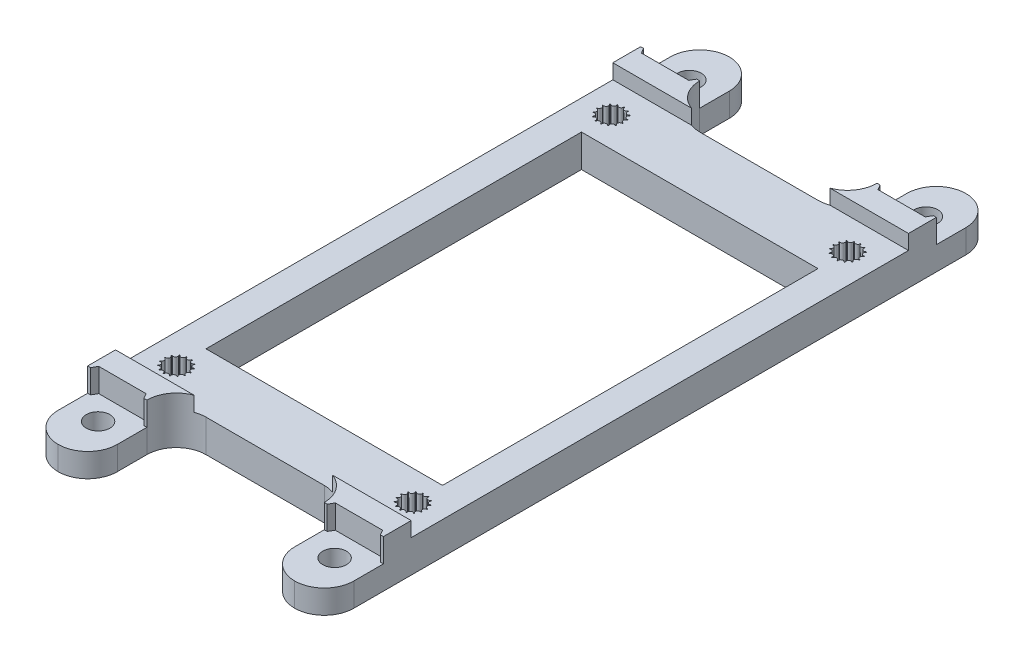
SolidWorks part; units mm, degrees
ref_plane "Front Plane" through (0, 0, 0) normal (0, 0, 1) x (1, 0, 0)
ref_plane "Top Plane" through (0, 0, 0) normal (0, 1, 0) x (1, 0, 0)
ref_plane "Right Plane" through (0, 0, 0) normal (1, 0, 0) x (0, 0, -1)
sketch "Sketch1" plane through (0, 0, 0) normal (0, 1, 0) x (1, 0, 0)
  line L1 (0, 0) -> (50, 0)
  line L2 (0, 0) -> (0, 83.5)
  line L3 (0, 83.5) -> (50, 83.5)
  line L4 (50, 0) -> (50, 83.5)
  dimension "D1" = 50
  dimension "D2" = 83.5
extrude "Boss-Extrude1" add sketch "Sketch1" along normal blind 8
sketch "Sketch2" plane through (0, 8, 0) normal (0, 1, 0) x (1, 0, 0)
  line L4 (0, 83.5) -> (0, 0)
  line L5 (0, 0) -> (50, 0)
  line L6 (50, 0) -> (50, 83.5)
  line L7 (50, 83.5) -> (0, 83.5)
  line L8 (0, 83.5) -> (0, 0)
  line L9 (0, 0) -> (50, 0)
  line L10 (50, 0) -> (50, 83.5)
  line L11 (50, 83.5) -> (0, 83.5)
  circle A0 centre (5, 5) radius 2.25
  circle A1 centre (5, 7.25) radius 0.4
  circle A2 centre (5.9152, 7.0555) radius 0.4
  circle A3 centre (6.6721, 6.5055) radius 0.4
  circle A4 centre (7.1399, 5.6953) radius 0.4
  circle A5 centre (7.2377, 4.7648) radius 0.4
  circle A6 centre (6.9486, 3.875) radius 0.4
  circle A7 centre (6.3225, 3.1797) radius 0.4
  circle A8 centre (5.4678, 2.7992) radius 0.4
  circle A9 centre (4.5322, 2.7992) radius 0.4
  circle A10 centre (3.6775, 3.1797) radius 0.4
  circle A11 centre (3.0514, 3.875) radius 0.4
  circle A12 centre (2.7623, 4.7648) radius 0.4
  circle A13 centre (2.8601, 5.6953) radius 0.4
  circle A14 centre (3.3279, 6.5055) radius 0.4
  circle A15 centre (4.0848, 7.0555) radius 0.4
  point P38 (5, 5)
  dimension "D4" = 4.5
  dimension "D5" = 0.8
  dimension "D2" = 5
  dimension "D3" = 5
  dimension "D1" = 0
  dimension "D6" = 15
extrude "Cut-Extrude1" cut sketch "Sketch2" against normal blind 8 contours A15 A0 A14 A13 A12 A11 A10 A9 A8 A7 A6 A5 A4 A3 A2 A1
ref_plane "Plane1" through (25, 0, 0) normal (-1, 0, 0) x (0, 0, 1)
ref_plane "Plane2" through (0, 0, -41.75) normal (0, 0, -1) x (-1, 0, 0)
mirror "Mirror1" about plane through (0, 0, -41.75) normal (0, 0, -1) of "Cut-Extrude1" second plane through (25, 0, 0) second plane normal (-1, 0, 0)
sketch "Sketch3" plane through (0, 8, 0) normal (0, 1, 0) x (1, 0, 0)
  line L1 (0, 0) -> (10, 0)
  line L2 (0, 0) -> (0, -15)
  line L3 (0, -15) -> (10, -15)
  line L4 (10, 0) -> (10, -15)
  circle A0 centre (5, -8.25) radius 2
  dimension "D3" = 4
  dimension "D1" = 15
  dimension "D2" = 10
  dimension "D4" = 5
  dimension "D5" = 8.25
extrude "Boss-Extrude2" add sketch "Sketch3" against normal blind 8
mirror "Mirror2" about plane through (0, 0, -41.75) normal (0, 0, -1) of "Boss-Extrude2" second plane through (25, 0, 0) second plane normal (-1, 0, 0)
fillet "Fillet1" radius 5 20 edges at (0, 4, 15) (10, 4, 0) (5, 0, 15) (10, 4, 15) (5, 8, 15) (45, 0, 15) (45, 8, 15) (50, 4, 15) (40, 4, 15) (40, 4, 0) (5, 0, -98.5) (5, 8, -98.5) (0, 4, -98.5) (10, 4, -98.5) (10, 4, -83.5) (50, 4, -98.5) (40, 4, -83.5) (45, 0, -98.5) (40, 4, -98.5) (45, 8, -98.5)
sketch "Sketch4" plane through (0, 8, 0) normal (0, 1, 0) x (1, 0, 0)
  line L0 (0.5, -5) -> (0, -5)
  line L1 (0, -5) -> (0.5, -5)
  line L2 (9.5, -5) -> (15, -5)
  line L3 (15, -5) -> (15, -18.6205)
  line L4 (15, -18.6205) -> (0, -18.6205)
  line L5 (0, -18.6205) -> (0, -5)
  line L6 (0.5, -5) -> (1, -4.134)
  line L7 (1, -4.134) -> (9, -4.134)
  line L8 (5, -5) -> (5, -3.4503) construction
  line L9 (9.5, -5) -> (9, -4.134)
  arc A0 (9.5, -5) -> (0.5, -5) centre (5, -5) ccw
  point P11 (5, -4.134)
  dimension "D1" = 9
  dimension "D2" = 4
  dimension "D3" = 1
extrude "Cut-Extrude2" cut sketch "Sketch4" against normal blind 4 contours L2 A0 L0 L5 L4 L3
mirror "Mirror4" about plane through (0, 0, -41.75) normal (0, 0, -1) of "Cut-Extrude2" second plane through (25, 0, 0) second plane normal (-1, 0, 0)
sketch "Sketch5" plane through (0, 8, 0) normal (0, 1, 0) x (1, 0, 0)
  line L0 (4.4, 41.75) -> (-4.4, 41.75) construction
  line L1 (5, 73.5) -> (45, 73.5)
  line L2 (5, 73.5) -> (5, 10)
  line L3 (5, 10) -> (45, 10)
  line L4 (45, 73.5) -> (45, 10)
  line L5 (5, 73.5) -> (45, 10) construction
  line L6 (5, 10) -> (45, 73.5) construction
  line L7 (25, 4.4) -> (25, -4.4) construction
  line L8 (50, -5) -> (50, 88.5) construction
  line L9 (35, 83.5) -> (15, 83.5) construction
  point P0 (25, 41.75)
  dimension "D1" = 5
  dimension "D2" = 10
extrude "Cut-Extrude3" cut sketch "Sketch5" against normal blind 13
sketch "Sketch6" plane through (0, 8, 0) normal (0, 1, 0) x (1, 0, 0)
  line L0 (3.025, 41.75) -> (-3.025, 41.75) construction
  line L1 (-0.55, -0.3) -> (50.55, -0.3)
  line L2 (-0.55, -0.3) -> (-0.55, 83.8)
  line L3 (-0.55, 83.8) -> (50.55, 83.8)
  line L4 (50.55, -0.3) -> (50.55, 83.8)
  line L5 (-0.55, -0.3) -> (50.55, 83.8) construction
  line L6 (-0.55, 83.8) -> (50.55, -0.3) construction
  line L7 (25, 73.5713) -> (25, 41.75) construction
  line L8 (25, 4.4) -> (25, -4.4) construction
  line L9 (25, 41.75) -> (31.28, 41.75) construction
  line L10 (31.28, 41.75) -> (23.1876, 41.75) construction
  point P0 (25, 41.75)
  point P7 (0, 0)
  dimension "D1" = 84.1
  dimension "D2" = 51.1
extrude "Cut-Extrude4" cut sketch "Sketch6" against normal blind 2.5 contours L1 L4 L3 L2
